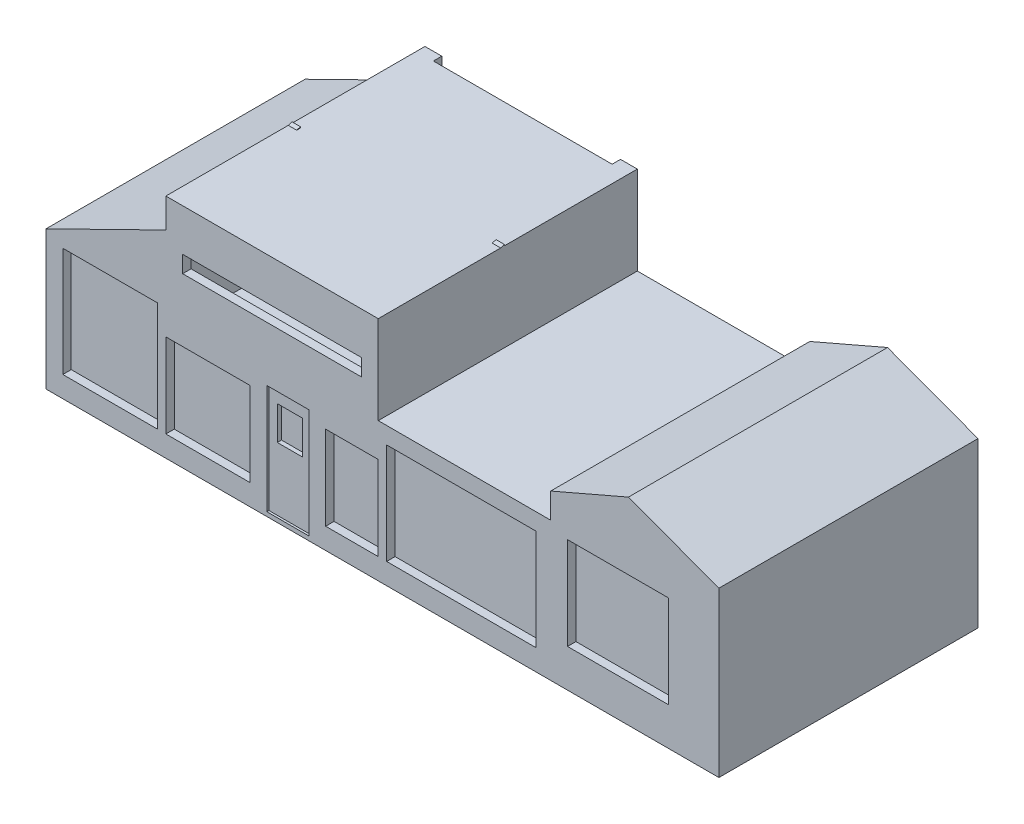
SolidWorks part; units mm, degrees
material "Plain Carbon Steel"
ref_plane "Front Plane" through (0, 0, 0) normal (0, 0, 1) x (1, 0, 0)
ref_plane "Top Plane" through (0, 0, 0) normal (0, 1, 0) x (1, 0, 0)
ref_plane "Right Plane" through (0, 0, 0) normal (1, 0, 0) x (0, 0, -1)
sketch "Sketch1" plane through (0, 0, 0) normal (0, 0, 1) x (1, 0, 0)
  line L1 (0, 0) -> (1016, 0)
  line L2 (0, 0) -> (0, 342.9)
  line L3 (0, 342.9) -> (1016, 342.9)
  line L4 (1016, 0) -> (1016, 342.9)
  dimension "D1" = 1016
  dimension "D2" = 342.9
extrude "Boss-Extrude1" add sketch "Sketch1" against normal blind 391.2
sketch "Right" plane through (0, 0, 0) normal (-1, 0, 0) x (0, 0, 1)
  line L8 (-25.4, 82.55) -> (-25.4, 184.15)
  line L9 (-25.4, 184.15) -> (-177.8, 184.15)
  line L10 (-177.8, 184.15) -> (-177.8, 82.55)
  line L11 (-177.8, 82.55) -> (-25.4, 82.55)
  line L16 (0, 0) -> (0, 209.55)
  line L17 (0, 209.55) -> (-203.2, 209.55)
  line L18 (-203.2, 209.55) -> (-203.2, 0)
  line L19 (-203.2, 0) -> (0, 0)
sketch "Front" plane through (0, 0, 0) normal (0, 0, 1) x (1, 0, 0)
  line L8 (0, 342.9) -> (0, 0)
  line L9 (0, 0) -> (1016, 0)
  line L10 (1016, 0) -> (1016, 342.9)
  line L11 (1016, 342.9) -> (0, 342.9)
  line L54 (1016, 0) -> (1016, 209.55)
  line L55 (0, 0) -> (1016, 0)
  line L56 (0, 209.55) -> (0, 0)
  line L57 (1016, 209.55) -> (501.65, 209.55)
  line L58 (501.65, 209.55) -> (501.65, 298.45)
  line L59 (501.65, 298.45) -> (180.975, 298.45)
  line L60 (0, 209.55) -> (180.975, 209.55)
  line L61 (180.975, 298.45) -> (180.975, 209.55)
  line L62 (180.975, 209.55) -> (0, 209.55)
  line L63 (180.975, 209.55) -> (180.975, 298.45)
  line L64 (180.975, 298.45) -> (0, 209.55)
  line L65 (25.4, 196.85) -> (168.275, 196.85)
  line L66 (168.275, 196.85) -> (25.4, 196.85)
  line L67 (168.275, 31.75) -> (168.275, 196.85)
  line L68 (25.4, 31.75) -> (168.275, 31.75)
  line L69 (25.4, 196.85) -> (25.4, 31.75)
  line L70 (25.4, 196.85) -> (25.4, 31.75)
  line L71 (762, 209.55) -> (1016, 209.55)
  line L72 (762, 247.65) -> (762, 209.55)
  line L73 (879.4142, 298.45) -> (762, 247.65)
  line L74 (1016, 247.65) -> (879.4142, 298.45)
  line L75 (1016, 209.55) -> (1016, 247.65)
  line L76 (501.65, 31.75) -> (501.65, 158.75)
  line L77 (501.65, 158.75) -> (422.275, 158.75)
  line L78 (422.275, 158.75) -> (422.275, 31.75)
  line L79 (422.275, 31.75) -> (501.65, 31.75)
  line L80 (333.375, 6.35) -> (396.875, 6.35)
  line L81 (396.875, 6.35) -> (396.875, 171.45)
  line L82 (396.875, 171.45) -> (333.375, 171.45)
  line L83 (333.375, 171.45) -> (333.375, 6.35)
  line L84 (180.975, 158.75) -> (180.975, 31.75)
  line L85 (307.975, 158.75) -> (180.975, 158.75)
  line L86 (307.975, 31.75) -> (307.975, 158.75)
  line L87 (180.975, 31.75) -> (307.975, 31.75)
  line L88 (476.25, 254) -> (476.25, 279.4)
  line L89 (476.25, 279.4) -> (206.375, 279.4)
  line L90 (206.375, 279.4) -> (206.375, 254)
  line L91 (206.375, 254) -> (476.25, 254)
  line L92 (787.4, 57.15) -> (939.8, 57.15)
  line L93 (787.4, 196.85) -> (787.4, 57.15)
  line L94 (939.8, 196.85) -> (787.4, 196.85)
  line L95 (939.8, 57.15) -> (939.8, 196.85)
  line L96 (514.35, 31.75) -> (739.775, 31.75)
  line L97 (514.35, 184.15) -> (514.35, 31.75)
  line L98 (739.775, 184.15) -> (514.35, 184.15)
  line L99 (739.775, 31.75) -> (739.775, 184.15)
sketch "Left" plane through (1016, 0, 0) normal (1, 0, 0) x (0, 0, -1)
  line L16 (190.5, 209.55) -> (190.5, 247.65)
  line L17 (190.5, 247.65) -> (12.7, 247.65)
  line L18 (203.2, 209.55) -> (203.2, 247.65)
  line L19 (203.2, 247.65) -> (190.5, 247.65)
  line L20 (190.5, 247.65) -> (190.5, 209.55)
  line L21 (12.7, 209.55) -> (190.5, 209.55)
  line L22 (190.5, 209.55) -> (203.2, 209.55)
  line L23 (12.7, 209.55) -> (12.7, 247.65)
  line L24 (0, 247.65) -> (0, 209.55)
  line L25 (12.7, 247.65) -> (0, 247.65)
  line L26 (12.7, 247.65) -> (12.7, 209.55)
  line L27 (0, 209.55) -> (12.7, 209.55)
  line L28 (203.2, 209.55) -> (0, 209.55)
  line L29 (203.2, 0) -> (203.2, 209.55)
  line L30 (0, 0) -> (203.2, 0)
  line L31 (0, 209.55) -> (0, 0)
sketch "Back" plane through (0, 0, -391.2) normal (0, 0, -1) x (-1, 0, 0)
  line L0 (-206.375, 342.9) -> (-476.25, 342.9)
  line L55 (-939.8, 196.85) -> (-939.8, 57.15)
  line L56 (-939.8, 57.15) -> (-787.4, 57.15)
  line L57 (-939.8, 196.85) -> (-939.8, 57.15)
  line L58 (-479.425, 158.75) -> (-479.425, 95.25)
  line L59 (-479.425, 95.25) -> (-314.325, 95.25)
  line L60 (-479.425, 95.25) -> (-314.325, 95.25)
  line L61 (-479.425, 158.75) -> (-479.425, 95.25)
  line L62 (-314.325, 158.75) -> (-479.425, 158.75)
  line L63 (-314.325, 95.25) -> (-314.325, 158.75)
  line L64 (-206.375, 241.3) -> (-206.375, 292.1)
  line L65 (-476.25, 241.3) -> (-206.375, 241.3)
  line L66 (-476.25, 241.3) -> (-206.375, 241.3)
  line L67 (-206.375, 292.1) -> (-476.25, 292.1)
  line L68 (-206.375, 292.1) -> (-476.25, 292.1)
  line L69 (-476.25, 292.1) -> (-476.25, 241.3)
  line L70 (-476.25, 292.1) -> (-476.25, 241.3)
  line L71 (-501.65, 298.45) -> (-501.65, 209.55)
  line L72 (-501.65, 209.55) -> (-1016, 209.55)
  line L73 (0, 0) -> (0, 209.55)
  line L74 (-1016, 0) -> (0, 0)
  line L75 (-1016, 209.55) -> (-1016, 0)
  line L76 (-180.975, 298.45) -> (-501.65, 298.45)
  line L77 (-488.95, 342.9) -> (-501.65, 342.9)
  line L78 (-501.65, 342.9) -> (-501.65, 298.45)
  line L79 (-501.65, 298.45) -> (-488.95, 298.45)
  line L80 (0, 209.55) -> (-180.975, 209.55)
  line L81 (-180.975, 209.55) -> (-180.975, 298.45)
  line L82 (-193.675, 298.45) -> (-180.975, 298.45)
  line L83 (-180.975, 298.45) -> (-180.975, 342.9)
  line L84 (0, 209.55) -> (-180.975, 298.45)
  line L85 (-180.975, 342.9) -> (-180.975, 298.45)
  line L86 (-180.975, 342.9) -> (-193.675, 342.9)
  line L87 (-488.95, 342.9) -> (-488.95, 298.45)
  line L88 (-488.95, 298.45) -> (-193.675, 298.45)
  line L89 (-488.95, 298.45) -> (-488.95, 342.9)
  line L90 (-193.675, 342.9) -> (-206.375, 342.9)
  line L91 (-206.375, 342.9) -> (-206.375, 304.8)
  line L92 (-206.375, 304.8) -> (-476.25, 304.8)
  line L93 (-476.25, 304.8) -> (-476.25, 342.9)
  line L94 (-476.25, 342.9) -> (-488.95, 342.9)
  line L95 (-193.675, 298.45) -> (-193.675, 342.9)
  line L96 (-193.675, 342.9) -> (-193.675, 298.45)
  line L97 (-787.4, 57.15) -> (-787.4, 196.85)
  line L98 (-787.4, 196.85) -> (-787.4, 57.15)
  line L99 (-787.4, 196.85) -> (-939.8, 196.85)
  line L100 (-787.4, 196.85) -> (-939.8, 196.85)
  line L101 (-1016, 209.55) -> (-762, 209.55)
  line L102 (-762, 209.55) -> (-762, 247.65)
  line L103 (-762, 247.65) -> (-879.4142, 298.45)
  line L104 (-879.4142, 298.45) -> (-1016, 247.65)
  line L105 (-1016, 247.65) -> (-1016, 209.55)
  line L106 (-590.55, 184.15) -> (-590.55, 158.75)
  line L107 (-590.55, 158.75) -> (-527.05, 158.75)
  line L108 (-527.05, 158.75) -> (-527.05, 184.15)
  line L109 (-527.05, 184.15) -> (-590.55, 184.15)
  line M1 (0, 0) -> (0, 342.9)
  line M2 (0, 342.9) -> (-1016, 342.9)
  line M3 (-1016, 342.9) -> (-1016, 0)
sketch "Sketch7" plane through (0, 0, -391.2) normal (0, 0, -1) x (-1, 0, 0)
  line L12 (-488.95, 361.95) -> (-488.95, 298.45)
  line L13 (-488.95, 298.45) -> (-193.675, 298.45)
  line L14 (-193.675, 298.45) -> (-193.675, 361.95)
  line L15 (-193.675, 361.95) -> (-488.95, 361.95)
  line L16 (-501.65, 361.95) -> (-501.65, 298.45)
  line L17 (-501.65, 298.45) -> (-488.95, 298.45)
  line L18 (-488.95, 298.45) -> (-488.95, 361.95)
  line L19 (-488.95, 361.95) -> (-501.65, 361.95)
  line L20 (-193.675, 361.95) -> (-193.675, 298.45)
  line L21 (-193.675, 298.45) -> (-180.975, 298.45)
  line L22 (-180.975, 298.45) -> (-180.975, 361.95)
  line L23 (-180.975, 361.95) -> (-193.675, 361.95)
  line L32 (-476.25, 292.1) -> (-476.25, 241.3)
  line L33 (-206.375, 292.1) -> (-476.25, 292.1)
  line L34 (-206.375, 241.3) -> (-206.375, 292.1)
  line L35 (-476.25, 241.3) -> (-206.375, 241.3)
  line L36 (-501.65, 298.45) -> (-501.65, 209.55)
  line L37 (-501.65, 209.55) -> (-1016, 209.55)
  line L38 (0, 209.55) -> (-180.975, 209.55)
  line L39 (-180.975, 209.55) -> (-180.975, 298.45)
extrude "Cut-Extrude1" cut sketch "Back" against normal through all contours L104 L103 L102 L72 L71 L78 M2 M3 | L84 L83 M1 M2 region at (75.4062, 294.7458, -391.2) region at (719.1949, 286.4423, -391.2)
sketch "Sketch11" plane through (29.8962, -69.0993, 0) normal (-0.3971, 0.9178, 0) x (0.9178, 0.3971, 0)
  line L12 (797.6879, 12.7) -> (925.6205, 12.7)
  line L13 (925.6205, 12.7) -> (925.6205, 190.5)
  line L14 (925.6205, 0) -> (925.6205, 12.7)
  line L15 (797.6879, 0) -> (925.6205, 0)
  line L16 (797.6879, 12.7) -> (797.6879, 0)
  line L17 (925.6205, 12.7) -> (797.6879, 12.7)
  line L18 (797.6879, 190.5) -> (797.6879, 12.7)
  line L19 (797.6879, 190.5) -> (925.6205, 190.5)
  line L20 (797.6879, 203.2) -> (797.6879, 190.5)
  line L21 (925.6205, 203.2) -> (797.6879, 203.2)
  line L22 (925.6205, 190.5) -> (925.6205, 203.2)
  line L23 (925.6205, 190.5) -> (797.6879, 190.5)
sketch "Sketch12" plane through (204.3794, 549.514, 0) normal (0.3486, 0.9373, 0) x (0.9373, -0.3486, 0)
  line L12 (865.9388, 190.5) -> (720.2119, 190.5)
  line L13 (720.2119, 190.5) -> (720.2119, 12.7)
  line L14 (720.2119, 203.2) -> (720.2119, 190.5)
  line L15 (865.9388, 203.2) -> (720.2119, 203.2)
  line L16 (865.9388, 190.5) -> (865.9388, 203.2)
  line L17 (720.2119, 190.5) -> (865.9388, 190.5)
  line L18 (865.9388, 12.7) -> (865.9388, 190.5)
  line L19 (720.2119, 12.7) -> (865.9388, 12.7)
  line L20 (865.9388, 0) -> (865.9388, 12.7)
  line L21 (720.2119, 0) -> (865.9388, 0)
  line L22 (720.2119, 12.7) -> (720.2119, 0)
  line L23 (865.9388, 12.7) -> (720.2119, 12.7)
extrude "Cut-Extrude4" cut sketch "Front" against normal blind 12.7 contours L90 L91 L88 L89 | L65 L69 L68 L67 | L84 L87 L86 L85 | L82 L83 L80 L81 | L78 L79 L76 L77 | L96 L99 L98 L97 | L92 L95 L94 L93 region at (96.8375, 114.3, 0) region at (461.9625, 95.25, 0) region at (365.125, 88.9, 0) region at (244.475, 95.25, 0) region at (341.3125, 266.7, 0) region at (863.6, 127, 0) region at (627.0625, 107.95, 0)
extrude "Cut-Extrude5" cut sketch "Right" against normal blind 12.7 contours L10 L11 L8 L9 region at (0, 133.35, -101.6)
extrude "Cut-Extrude6" cut sketch "Back<3>" against normal blind 12.7 contours L97 L99 L55 L56 | L108 L109 L106 L107 | L59 L63 L62 L58 | L93 L92 L91 M2 | L67 L69 L65 L64 region at (341.3125, 323.85, -391.2) region at (863.6, 127, -391.2) region at (396.875, 127, -391.2) region at (341.3125, 266.7, -391.2) region at (558.8, 171.45, -391.2)
sketch "Back<3>" plane through (0, 0, -391.2) normal (0, 0, -1) x (-1, 0, 0) same geometry as "Back"
sketch "Sketch18" plane through (0, 6.35, 0) normal (0, 1, 0) x (1, 0, 0)
  line L0 (193.675, 139.7) -> (244.475, 139.7)
  line L1 (1016, 190.5) -> (879.4142, 190.5) construction
  line L2 (333.375, 0) -> (396.875, 0)
  line L3 (396.875, 0) -> (396.875, 12.7)
  line L4 (396.875, 12.7) -> (965.2, 12.7)
  line L5 (396.875, 12.7) -> (396.875, 0) construction
  line L6 (333.375, 0) -> (396.875, 0) construction
  line L7 (0, 391.2) -> (1016, 391.2)
  line L8 (0, 391.2) -> (0, 0)
  line L9 (0, 0) -> (1016, 0)
  line L10 (1016, 391.2) -> (1016, 0)
  line L11 (12.7, 378.5) -> (1003.3, 378.5)
  line L12 (12.7, 378.5) -> (12.7, 12.7)
  line L13 (12.7, 12.7) -> (1003.3, 12.7)
  line L14 (1003.3, 378.5) -> (1003.3, 12.7)
  line L15 (492.125, 378.5) -> (492.125, 63.5)
  line L16 (692.15, 378.5) -> (692.15, 261.025)
  line L17 (501.65, 378.5) -> (501.65, 139.7)
  line L18 (518.8898, 139.7) -> (501.65, 139.7)
  line L19 (974.725, 378.5) -> (974.725, 12.7)
  line L20 (501.65, 130.175) -> (568.325, 130.175)
  line L21 (692.15, 261.025) -> (641.35, 261.025)
  line L22 (501.65, 130.175) -> (501.65, 73.025)
  line L23 (701.675, 292.775) -> (752.475, 292.775)
  line L24 (701.675, 292.775) -> (701.675, 261.025)
  line L25 (701.675, 261.025) -> (752.475, 261.025)
  line L26 (752.475, 292.775) -> (752.475, 261.025)
  line L27 (501.65, 73.025) -> (568.325, 73.025)
  line L28 (568.325, 130.175) -> (568.325, 73.025)
  line L29 (965.2, 38.1) -> (965.2, 165.1)
  line L30 (657.098, 311.825) -> (692.15, 311.825)
  line L31 (518.8898, 365.8) -> (518.8898, 152.4)
  line L32 (501.65, 63.5) -> (501.65, 12.7)
  line L33 (774.7, 378.5) -> (774.7, 12.7)
  line L34 (180.975, 378.5) -> (180.975, 12.7)
  line L35 (180.975, 0) -> (180.975, 391.2) construction
  line L36 (501.65, 0) -> (501.65, 391.2) construction
  line L37 (441.325, 114.3) -> (492.125, 114.3)
  line L38 (295.275, 139.7) -> (358.775, 139.7)
  line L39 (295.275, 139.7) -> (295.275, 378.5)
  line L40 (295.275, 378.5) -> (358.775, 378.5)
  line L41 (358.775, 139.7) -> (358.775, 378.5)
  line L42 (358.775, 378.5) -> (396.875, 378.5)
  line L43 (358.775, 378.5) -> (358.775, 139.7)
  line L44 (358.775, 139.7) -> (396.875, 139.7)
  line L45 (396.875, 378.5) -> (396.875, 139.7)
  line L46 (396.875, 378.5) -> (441.325, 378.5)
  line L47 (396.875, 378.5) -> (396.875, 139.7)
  line L48 (396.875, 139.7) -> (441.325, 139.7)
  line L49 (441.325, 378.5) -> (441.325, 139.7)
  line L50 (400.05, 177.8) -> (438.15, 177.8)
  line L51 (400.05, 177.8) -> (400.05, 152.4)
  line L52 (400.05, 152.4) -> (438.15, 152.4)
  line L53 (438.15, 177.8) -> (438.15, 152.4)
  line L54 (311.15, 365.8) -> (342.9, 365.8) construction
  line L55 (311.15, 365.8) -> (311.15, 340.4) construction
  line L56 (311.15, 340.4) -> (342.9, 340.4) construction
  line L57 (342.9, 365.8) -> (342.9, 340.4) construction
  line L58 (492.125, 63.5) -> (441.325, 63.5)
  line L59 (501.65, 63.5) -> (492.125, 63.5)
  line L60 (577.85, 63.5) -> (501.65, 63.5)
  line L61 (552.45, 130.175) -> (552.45, 79.375)
  line L62 (552.45, 79.375) -> (501.65, 79.375)
  line L89 (752.475, 184.15) -> (752.475, 378.5)
  line L90 (752.475, 378.5) -> (701.675, 378.5)
  line L91 (701.675, 378.5) -> (701.675, 302.3)
  line L92 (701.675, 302.3) -> (752.475, 302.3)
  line L93 (752.475, 302.3) -> (752.475, 308.65)
  line L94 (752.475, 308.65) -> (762, 308.65)
  line L95 (762, 308.65) -> (762, 251.5)
  line L96 (762, 251.5) -> (641.35, 251.5)
  line L97 (641.35, 251.5) -> (641.35, 311.825)
  line L98 (641.35, 311.825) -> (657.098, 311.825)
  line L99 (625.348, 343.575) -> (625.348, 378.5)
  line L100 (625.348, 378.5) -> (518.8898, 378.5)
  line L101 (518.8898, 378.5) -> (518.8898, 365.8)
  line L102 (518.8898, 152.4) -> (518.8898, 139.7)
  line L103 (518.8898, 139.7) -> (577.85, 139.7)
  line L104 (577.85, 139.7) -> (577.85, 63.5)
  line L106 (441.325, 63.5) -> (441.325, 139.7)
  line L107 (441.325, 139.7) -> (295.275, 139.7)
  line L108 (295.275, 139.7) -> (295.275, 88.9)
  line L109 (244.475, 88.9) -> (244.475, 190.5)
  line L110 (244.475, 190.5) -> (193.675, 190.5)
  line L111 (193.675, 190.5) -> (193.675, 139.7)
  line L112 (193.675, 139.7) -> (146.05, 139.7)
  line L113 (146.05, 139.7) -> (146.05, 165.1)
  line L114 (146.05, 165.1) -> (12.7, 165.1)
  line L115 (12.7, 165.1) -> (12.7, 152.4)
  line L116 (12.7, 152.4) -> (63.5, 152.4)
  line L117 (63.5, 152.4) -> (63.5, 63.5)
  line L118 (63.5, 63.5) -> (152.4, 63.5)
  line L119 (152.4, 63.5) -> (152.4, 12.7)
  line L120 (152.4, 12.7) -> (333.375, 12.7)
  line L121 (333.375, 12.7) -> (333.375, 0)
  line L125 (965.2, 12.7) -> (965.2, 38.1)
  line L126 (965.2, 38.1) -> (800.1, 38.1)
  line L127 (800.1, 38.1) -> (800.1, 165.1)
  line L128 (800.1, 165.1) -> (965.2, 165.1)
  line L129 (965.2, 165.1) -> (965.2, 190.5)
  line L130 (965.2, 190.5) -> (762, 190.5)
  line L131 (762, 190.5) -> (762, 184.15)
  line L132 (762, 184.15) -> (752.475, 184.15)
  circle A0 centre (311.15, 365.8) radius 9.525
  circle A1 centre (342.9, 365.8) radius 9.525
  circle A2 centre (311.15, 340.4) radius 9.525
  circle A3 centre (342.9, 340.4) radius 9.525
  arc A4 (625.348, 343.575) -> (657.098, 311.825) centre (657.098, 343.575) ccw
  arc A5 (244.475, 88.9) -> (295.275, 88.9) centre (269.875, 88.9) ccw
  ellipse E2 centre (524.1595, 259.1) end of major axis (524.1595, 150.8298) minor radius 31.0548 (518.8898, 152.4) -> (518.8898, 365.8) ccw
  dimension "D24" = 25.4
  dimension "D41" = 31.75
  dimension "D74" = 19.05
  dimension "D75" = 19.05
  dimension "D76" = 19.05
  dimension "D77" = 19.05
  dimension "D80" = 12.7
  dimension "D1" = 63.5
  dimension "D2" = 180.975
  dimension "D3" = 88.9
  dimension "D4" = 50.8
  dimension "D5" = 133.35
  dimension "D6" = 47.625
  dimension "D7" = 50.8
  dimension "D8" = 146.05
  dimension "D9" = 136.525
  dimension "D10" = 76.2
  dimension "D11" = 106.4582
  dimension "D12" = 165.1
  dimension "D13" = 9.525
  dimension "D14" = 120.65
  dimension "D15" = 15.748
  dimension "D16" = 50.8
  dimension "D17" = 9.525
  dimension "D18" = 9.525
  dimension "D19" = 50.8
  dimension "D20" = 203.2
  dimension "D21" = 25.4
  dimension "D22" = 76.2
  dimension "D23" = 12.7
  dimension "D25" = 12.7
  dimension "D26" = 25.4
  dimension "D27" = 50.8
  dimension "D28" = 50.8
  dimension "D29" = 101.6
  dimension "D30" = 76.2
  dimension "D31" = 34.925
  dimension "D32" = 60.325
  dimension "D33" = 57.15
  dimension "D34" = 6.35
  dimension "D35" = 76.2
  dimension "D36" = 25.4
  dimension "D37" = 568.325
  dimension "D38" = 12.7
  dimension "D39" = 50.8
  dimension "D40" = 88.9
  dimension "D42" = 12.7
  dimension "D43" = 12.7
  dimension "D44" = 12.7
  dimension "D45" = 12.7
  dimension "D46" = 6.35
  dimension "D47" = 9.525
  dimension "D48" = 9.525
  dimension "D49" = 25.4
  dimension "D50" = 238.8
  dimension "D51" = 38.1
  dimension "D52" = 25.4
  dimension "D53" = 9.525
  dimension "D54" = 9.525
  dimension "D55" = 50.8
  dimension "D56" = 9.525
  dimension "D57" = 9.525
  dimension "D58" = 9.525
  dimension "D59" = 9.525
  dimension "D60" = 50.8
  dimension "D61" = 9.525
  dimension "D62" = 9.525
  dimension "D63" = 9.525
  dimension "D64" = 63.5
  dimension "D66" = 35.052
  dimension "D67" = 38.1
  dimension "D68" = 44.45
  dimension "D69" = 38.1
  dimension "D70" = 25.4
  dimension "D71" = 3.175
  dimension "D72" = 12.7
  dimension "D73" = 238.8
  dimension "D78" = 31.75
  dimension "D79" = 25.4
  dimension "D81" = 15.875
  dimension "D82" = 50.8
  dimension "D83" = 50.8
  dimension "D84" = 50.8
  dimension "D86" = 50.8
sketch "Sketch19" plane through (0, 6.35, 0) normal (0, 1, 0) x (1, 0, 0)
  line L0 (295.275, 139.7) -> (250.825, 139.7)
  line L1 (307.975, 378.5) -> (307.975, 139.7)
  line L2 (12.7, 378.5) -> (1003.3, 378.5) construction
  line L3 (441.325, 139.7) -> (295.275, 139.7) construction
  line L18 (250.825, 190.5) -> (250.825, 139.7)
  line L19 (250.825, 139.7) -> (244.475, 139.7)
  line L20 (244.475, 139.7) -> (244.475, 88.9)
  line L21 (295.275, 88.9) -> (295.275, 139.7)
  line L22 (295.275, 139.7) -> (441.325, 139.7)
  line L23 (441.325, 139.7) -> (441.325, 127)
  line L24 (441.325, 127) -> (492.125, 127)
  line L25 (492.125, 127) -> (492.125, 190.5)
  line L26 (492.125, 190.5) -> (250.825, 190.5)
  line L172 (25.4, 12.7) -> (25.4, 15.24)
  line L173 (25.4, 15.24) -> (152.4, 15.24)
  line L174 (152.4, 15.24) -> (152.4, 63.5)
  line L175 (152.4, 63.5) -> (142.24, 63.5)
  line L176 (142.24, 63.5) -> (142.24, 22.86)
  line L177 (142.24, 22.86) -> (22.86, 22.86)
  line L178 (22.86, 22.86) -> (22.86, 142.24)
  line L179 (22.86, 142.24) -> (63.5, 142.24)
  line L180 (63.5, 142.24) -> (63.5, 152.4)
  line L181 (63.5, 152.4) -> (12.7, 152.4)
  line L182 (12.7, 152.4) -> (12.7, 25.4)
  line L183 (12.7, 25.4) -> (12.7, 12.7)
  line L184 (12.7, 12.7) -> (25.4, 12.7)
  line L185 (22.86, 22.86) -> (142.24, 22.86)
  line L186 (142.24, 22.86) -> (142.24, 63.5)
  line L187 (142.24, 63.5) -> (63.5, 63.5)
  line L188 (63.5, 63.5) -> (63.5, 142.24)
  line L189 (63.5, 142.24) -> (22.86, 142.24)
  line L190 (22.86, 142.24) -> (22.86, 22.86)
  line L191 (82.55, 114.3) -> (82.55, 82.55)
  line L192 (82.55, 82.55) -> (133.35, 82.55)
  line L193 (133.35, 82.55) -> (133.35, 114.3)
  line L194 (133.35, 114.3) -> (82.55, 114.3)
  line L195 (518.8898, 139.7) -> (518.8898, 153.0623)
  line L196 (518.8898, 177.1377) -> (518.8898, 190.5)
  line L197 (518.8898, 190.5) -> (501.65, 190.5)
  line L198 (501.65, 190.5) -> (501.65, 139.7)
  line L199 (501.65, 139.7) -> (518.8898, 139.7)
  line L200 (692.15, 190.5) -> (627.888, 190.5)
  line L201 (627.888, 190.5) -> (627.888, 155.575)
  line L202 (657.098, 126.365) -> (692.15, 126.365)
  line L203 (692.15, 126.365) -> (692.15, 190.5)
  line L204 (627.888, 155.575) -> (627.888, 190.5)
  line L205 (627.888, 190.5) -> (625.348, 190.5)
  line L206 (625.348, 190.5) -> (625.348, 155.575)
  line L207 (657.098, 123.825) -> (692.15, 123.825)
  line L208 (692.15, 123.825) -> (692.15, 126.365)
  line L209 (692.15, 126.365) -> (657.098, 126.365)
  line L210 (657.098, 123.825) -> (641.35, 123.825)
  line L211 (641.35, 123.825) -> (641.35, 73.025)
  line L212 (641.35, 73.025) -> (692.15, 73.025)
  line L213 (692.15, 73.025) -> (692.15, 123.825)
  line L214 (692.15, 123.825) -> (657.098, 123.825)
  line L215 (752.475, 73.025) -> (752.475, 104.775)
  line L216 (752.475, 104.775) -> (701.675, 104.775)
  line L217 (701.675, 104.775) -> (701.675, 73.025)
  line L218 (701.675, 73.025) -> (752.475, 73.025)
  line L219 (800.1, 165.1) -> (800.1, 38.1)
  line L220 (800.1, 38.1) -> (939.8, 38.1)
  line L221 (939.8, 38.1) -> (939.8, 165.1)
  line L222 (939.8, 165.1) -> (800.1, 165.1)
  line L223 (965.2, 38.1) -> (965.2, 165.1)
  line L224 (965.2, 165.1) -> (800.1, 165.1)
  line L225 (800.1, 165.1) -> (800.1, 38.1)
  line L226 (800.1, 38.1) -> (965.2, 38.1)
  line L227 (974.725, 12.7) -> (1003.3, 12.7)
  line L228 (1003.3, 12.7) -> (1003.3, 190.5)
  line L229 (1003.3, 190.5) -> (974.725, 190.5)
  line L230 (974.725, 190.5) -> (974.725, 12.7)
  line L231 (501.65, 130.175) -> (501.65, 73.025)
  line L232 (501.65, 73.025) -> (568.325, 73.025)
  line L233 (568.325, 73.025) -> (568.325, 130.175)
  line L234 (568.325, 130.175) -> (501.65, 130.175)
  arc A2 (244.475, 88.9) -> (295.275, 88.9) centre (269.875, 88.9) ccw
  arc A10 (627.888, 155.575) -> (657.098, 126.365) centre (657.098, 155.575) ccw
  arc A11 (625.348, 155.575) -> (657.098, 123.825) centre (657.098, 155.575) ccw
  arc A12 (627.888, 155.575) -> (657.098, 126.365) centre (657.098, 155.575) ccw
  ellipse E6 centre (539.75, 165.1) end of major axis (570.23, 165.1) minor radius 16.51 (518.8898, 153.0623) -> (518.8898, 177.1377) ccw
  dimension "D10" = 25.4
  dimension "D1" = 63.5
  dimension "D2" = 9.525
  dimension "D3" = 241.3
  dimension "D4" = 50.8
  dimension "D5" = 6.35
  dimension "D6" = 146.05
  dimension "D7" = 50.8
  dimension "D8" = 12.7
extrude "Cut-Extrude12" cut sketch "Sketch19" along normal blind 101.6 from offset 76.2 contours L198 L199 L197 | L223 L221 | L212 L213 L207 | L221 L222 L219 L220 | L201 A10 L202 L203 L200 | L233 L234 L231 L232 | L217 L218 L215 L216 | L194 L191 L192 L193 region at (530.2728, 6.35, -165.1) region at (661.2095, 6.35, -159.6201) region at (666.75, 6.35, -98.425) region at (727.075, 6.35, -88.9) region at (869.95, 6.35, -101.6) region at (952.5, 6.35, -101.6) region at (534.9875, 6.35, -101.6)
sketch "Sketch31" plane through (0, 171.45, 0) normal (0, -1, 0) x (1, 0, 0)
  line L30 (701.675, -73.025) -> (701.675, -104.775)
  line L31 (701.675, -104.775) -> (752.475, -104.775)
  line L32 (752.475, -104.775) -> (752.475, -73.025)
  line L33 (752.475, -73.025) -> (701.675, -73.025)
  line L34 (692.15, -73.025) -> (641.35, -73.025)
  line L35 (641.35, -73.025) -> (641.35, -123.825)
  line L36 (641.35, -123.825) -> (692.15, -123.825)
  line L37 (692.15, -123.825) -> (692.15, -73.025)
  line L38 (627.888, -155.575) -> (627.888, -190.5)
  line L39 (627.888, -190.5) -> (692.15, -190.5)
  line L40 (692.15, -190.5) -> (692.15, -126.365)
  line L41 (692.15, -126.365) -> (657.098, -126.365)
  line L42 (568.325, -130.175) -> (568.325, -73.025)
  line L43 (568.325, -73.025) -> (501.65, -73.025)
  line L44 (501.65, -73.025) -> (501.65, -130.175)
  line L45 (501.65, -130.175) -> (568.325, -130.175)
  line L46 (244.475, -190.5) -> (492.125, -190.5)
  line L47 (518.8898, -190.5) -> (501.65, -190.5)
  line L48 (692.15, -126.365) -> (692.15, -123.825)
  line L49 (627.888, -190.5) -> (625.348, -190.5)
  line L50 (939.8, -165.1) -> (939.8, -38.1)
  line L51 (965.2, -38.1) -> (965.2, -165.1)
  line L52 (577.85, -139.7) -> (577.85, -190.5)
  line L53 (295.275, -139.7) -> (244.475, -139.7)
  line L90 (396.875, 0) -> (333.375, 0)
  line L91 (396.875, -12.7) -> (396.875, 0)
  line L92 (965.2, -12.7) -> (396.875, -12.7)
  line L93 (965.2, -38.1) -> (965.2, -12.7)
  line L94 (800.1, -38.1) -> (965.2, -38.1)
  line L95 (800.1, -165.1) -> (800.1, -38.1)
  line L96 (965.2, -165.1) -> (800.1, -165.1)
  line L97 (965.2, -190.5) -> (965.2, -165.1)
  line L98 (762, -190.5) -> (965.2, -190.5)
  line L99 (762, -184.15) -> (762, -190.5)
  line L100 (752.475, -184.15) -> (762, -184.15)
  line L101 (752.475, -190.5) -> (752.475, -184.15)
  line L102 (701.675, -190.5) -> (752.475, -190.5)
  line L103 (701.675, -114.3) -> (701.675, -190.5)
  line L104 (752.475, -114.3) -> (701.675, -114.3)
  line L105 (752.475, -120.65) -> (752.475, -114.3)
  line L106 (762, -120.65) -> (752.475, -120.65)
  line L107 (762, -63.5) -> (762, -120.65)
  line L108 (641.35, -63.5) -> (762, -63.5)
  line L109 (641.35, -123.825) -> (641.35, -63.5)
  line L110 (657.098, -123.825) -> (641.35, -123.825)
  line L111 (625.348, -190.5) -> (625.348, -155.575)
  line L112 (518.8898, -190.5) -> (625.348, -190.5)
  line L113 (518.8898, -177.1377) -> (518.8898, -190.5)
  line L114 (518.8898, -139.7) -> (518.8898, -153.0623)
  line L115 (577.85, -139.7) -> (518.8898, -139.7)
  line L116 (577.85, -63.5) -> (577.85, -139.7)
  line L117 (441.325, -63.5) -> (577.85, -63.5)
  line L118 (441.325, -139.7) -> (441.325, -63.5)
  line L119 (295.275, -139.7) -> (441.325, -139.7)
  line L120 (295.275, -88.9) -> (295.275, -139.7)
  line L121 (244.475, -190.5) -> (244.475, -88.9)
  line L122 (193.675, -190.5) -> (244.475, -190.5)
  line L123 (193.675, -139.7) -> (193.675, -190.5)
  line L124 (146.05, -139.7) -> (193.675, -139.7)
  line L125 (146.05, -165.1) -> (146.05, -139.7)
  line L126 (12.7, -165.1) -> (146.05, -165.1)
  line L127 (12.7, -152.4) -> (12.7, -165.1)
  line L128 (63.5, -152.4) -> (12.7, -152.4)
  line L129 (63.5, -63.5) -> (63.5, -152.4)
  line L130 (152.4, -63.5) -> (63.5, -63.5)
  line L131 (152.4, -12.7) -> (152.4, -63.5)
  line L132 (333.375, -12.7) -> (152.4, -12.7)
  line L133 (333.375, 0) -> (333.375, -12.7)
  line L134 (1016, 0) -> (0, 0)
  line L135 (0, 0) -> (0, -203.2)
  line L136 (0, -203.2) -> (1016, -203.2)
  line L137 (1016, -203.2) -> (1016, 0)
  line L186 (180.9126, -12.7) -> (180.9126, -190.5)
  line L187 (180.9126, -190.5) -> (244.475, -190.5)
  line L188 (244.475, -190.5) -> (244.475, -88.9)
  line L189 (295.275, -88.9) -> (295.275, -139.7)
  line L190 (295.275, -139.7) -> (441.325, -139.7)
  line L191 (441.325, -139.7) -> (441.325, -127)
  line L192 (441.325, -127) -> (441.325, -63.5)
  line L193 (441.325, -63.5) -> (577.85, -63.5)
  line L194 (577.85, -63.5) -> (577.85, -139.7)
  line L195 (577.85, -139.7) -> (518.8898, -139.7)
  line L196 (518.8898, -139.7) -> (518.8898, -153.0623)
  line L197 (518.8898, -177.1377) -> (518.8898, -190.5)
  line L198 (518.8898, -190.5) -> (625.348, -190.5)
  line L199 (625.348, -190.5) -> (625.348, -155.575)
  line L200 (657.098, -123.825) -> (641.35, -123.825)
  line L201 (641.35, -123.825) -> (641.35, -73.025)
  line L202 (641.35, -73.025) -> (641.35, -63.5)
  line L203 (641.35, -63.5) -> (762, -63.5)
  line L204 (762, -63.5) -> (762, -120.65)
  line L205 (762, -120.65) -> (752.475, -120.65)
  line L206 (752.475, -120.65) -> (752.475, -114.3)
  line L207 (752.475, -114.3) -> (701.675, -114.3)
  line L208 (701.675, -114.3) -> (701.675, -190.5)
  line L209 (701.675, -190.5) -> (752.475, -190.5)
  line L210 (752.475, -190.5) -> (752.475, -184.15)
  line L211 (752.475, -184.15) -> (762, -184.15)
  line L212 (762, -184.15) -> (762, -190.5)
  line L213 (762, -190.5) -> (787.4, -190.5)
  line L214 (787.4, -190.5) -> (939.8, -190.5)
  line L215 (939.8, -190.5) -> (965.2, -190.5)
  line L216 (965.2, -190.5) -> (965.2, -165.1)
  line L217 (965.2, -165.1) -> (939.8, -165.1)
  line L218 (939.8, -165.1) -> (800.1, -165.1)
  line L219 (800.1, -165.1) -> (800.1, -38.1)
  line L220 (800.1, -38.1) -> (939.8, -38.1)
  line L221 (939.8, -38.1) -> (965.2, -38.1)
  line L222 (965.2, -38.1) -> (965.2, -12.7)
  line L223 (965.2, -12.7) -> (939.8, -12.7)
  line L224 (939.8, -12.7) -> (787.4, -12.7)
  line L225 (787.4, -12.7) -> (739.775, -12.7)
  line L226 (739.775, -12.7) -> (514.35, -12.7)
  line L227 (514.35, -12.7) -> (501.65, -12.7)
  line L228 (501.65, -12.7) -> (422.275, -12.7)
  line L229 (422.275, -12.7) -> (396.875, -12.7)
  line L230 (396.875, -12.7) -> (333.375, -12.7)
  line L231 (333.375, -12.7) -> (307.975, -12.7)
  line L232 (307.975, -12.7) -> (180.975, -12.7)
  line L233 (180.975, -12.7) -> (180.9126, -12.7)
  line L234 (701.675, -104.775) -> (701.675, -73.025)
  line L235 (692.15, -73.025) -> (692.15, -123.825)
  line L236 (692.15, -126.365) -> (692.15, -190.5)
  line L237 (568.325, -130.175) -> (501.65, -130.175)
  line L238 (492.125, -127) -> (492.125, -190.5)
  line L239 (501.65, -190.5) -> (501.65, -139.7)
  line L240 (501.65, -139.7) -> (518.8898, -139.7)
  line L241 (441.325, -127) -> (492.125, -127)
  line L242 (501.65, -190.5) -> (492.125, -190.5)
  line L244 (492.125, -127) -> (492.125, -63.5)
  arc A1 (657.098, -126.365) -> (627.888, -155.575) centre (657.098, -155.575) ccw
  arc A4 (657.098, -123.825) -> (625.348, -155.575) centre (657.098, -155.575) ccw
  arc A5 (295.275, -88.9) -> (244.475, -88.9) centre (269.875, -88.9) ccw
  arc A8 (295.275, -88.9) -> (244.475, -88.9) centre (269.875, -88.9) ccw
  arc A9 (657.098, -123.825) -> (625.348, -155.575) centre (657.098, -155.575) ccw
  ellipse E2 centre (539.75, -165.1) end of major axis (570.23, -165.1) minor radius 16.51 (518.8898, -177.1377) -> (518.8898, -153.0623) ccw
  ellipse E4 centre (539.75, -165.1) end of major axis (570.23, -165.1) minor radius 16.51 (518.8898, -177.1377) -> (518.8898, -153.0623) ccw
sketch "Sketch36" plane through (0, 0, -12.7) normal (0, 0, 1) x (1, 0, 0)
  line L8 (206.375, 279.4) -> (206.375, 254)
  line L9 (206.375, 254) -> (476.25, 254)
  line L10 (476.25, 254) -> (476.25, 279.4)
  line L11 (476.25, 279.4) -> (206.375, 279.4)
  line L18 (488.7994, 177.8) -> (193.675, 177.8)
  line L19 (193.675, 177.8) -> (193.675, 298.45)
  line L20 (193.675, 298.45) -> (488.95, 298.45)
  line L21 (488.95, 298.45) -> (488.95, 254)
  line L22 (488.95, 254) -> (476.25, 254)
  line L23 (476.25, 254) -> (476.25, 279.4)
  line L24 (476.25, 279.4) -> (206.375, 279.4)
  line L25 (206.375, 279.4) -> (206.375, 254)
  line L26 (206.375, 254) -> (488.7994, 254)
  line L27 (488.7994, 254) -> (488.7994, 177.8)
  line M5 (206.375, 279.4) -> (206.375, 254)
  line M6 (206.375, 254) -> (476.25, 254)
  line M7 (476.25, 254) -> (476.25, 279.4)
  line M8 (476.25, 279.4) -> (206.375, 279.4)
extrude "top room" cut sketch "Sketch36" against normal blind 177.8 contours L27 L22 L21 L20 L19 L18 M6 M5 M8 M7 | L9 M8 M5 M6 M7 region at (341.3125, 266.7, -12.7) region at (341.2536, 231.3228, -12.7)
sketch "Sketch39" plane through (180.975, 0, 0) normal (-1, 0, 0) x (0, 0, 1)
  line L7 (-190.5, 298.45) -> (-190.5, 344.6756)
  line L8 (-184.8182, 342.9) -> (-190.5, 342.9)
  line L9 (-190.5, 344.6756) -> (-83.2182, 311.15)
  line M2 (0, 342.9) -> (-391.2, 342.9)
  dimension "D1" = 46.2256
extrude "topsaide" add sketch "Sketch39" against normal blind 12.7 contours M2 region at (180.975, 343.4919, -188.6061)
sketch "Sketch40" plane through (501.65, 0, 0) normal (1, 0, 0) x (0, 0, -1)
  line L3 (190.5, 298.45) -> (190.5, 344.6756)
  line L4 (184.8182, 342.9) -> (190.5, 342.9)
  line L5 (190.5, 344.6756) -> (83.2182, 311.15)
  line M1 (391.2, 342.9) -> (0, 342.9)
extrude "topside" add sketch "Sketch40" against normal blind 12.7 contours M1 region at (501.65, 343.4919, -188.6061)
sketch "Sketch49" plane through (0, 171.45, 0) normal (0, 1, 0) x (1, 0, 0)
  line L0 (488.95, 139.7) -> (488.95, 190.5)
  line L5 (441.325, 139.7) -> (488.95, 139.7)
  line L8 (488.95, 139.7) -> (488.95, 190.5)
  line L10 (317.5, 190.5) -> (317.5, 139.7)
  line L11 (488.95, 190.5) -> (317.5, 190.5)
  line L18 (317.5, 139.7) -> (441.325, 139.7)
sketch "Sketch42" plane through (0, 6.35, 0) normal (0, 1, 0) x (1, 0, 0)
  line L4 (82.55, 114.3) -> (82.55, 82.55)
  line L5 (82.55, 82.55) -> (133.35, 82.55)
  line L6 (133.35, 82.55) -> (133.35, 114.3)
  line L7 (133.35, 114.3) -> (82.55, 114.3)
extrude "table" add sketch "Sketch42" along normal blind 50.8
extrude "Cut-Extrude35" cut sketch "Sketch31" along normal blind 88.9 contours L113 E2 L114 L240 L239 L47 | L44 L45 L42 L43 | L41 A1 L38 L39 L40 | L36 L37 L34 L35 | L32 L33 L30 L31 | L53 region at (727.075, 171.45, -88.9) region at (666.75, 171.45, -98.425) region at (661.2095, 171.45, -159.6201) region at (530.2728, 171.45, -165.1) region at (269.875, 171.45, -104.0983) region at (534.9875, 171.45, -101.6)
extrude "Cut-Extrude36" cut sketch "Sketch31<7>" along normal blind 114.3 contours E2 L113 L112 L52 L115 L114 | L113 E2 L114 L240 L239 L47 region at (548.3699, 171.45, -189.7217) region at (530.2728, 171.45, -165.1)
sketch "Sketch31<7>" plane through (0, 171.45, 0) normal (0, -1, 0) x (1, 0, 0) same geometry as "Sketch31"
sketch "Sketch76" plane through (0, 0, 0) normal (0, 0, 1) x (1, 0, 0)
  line L1 (333.375, 171.45) -> (396.875, 171.45)
  line L2 (333.375, 171.45) -> (333.375, 6.35)
  line L3 (333.375, 6.35) -> (396.875, 6.35)
  line L4 (396.875, 171.45) -> (396.875, 6.35)
  line L5 (346.075, 152.4) -> (384.175, 152.4)
  line L6 (346.075, 152.4) -> (346.075, 101.6)
  line L7 (346.075, 101.6) -> (384.175, 101.6)
  line L8 (384.175, 152.4) -> (384.175, 101.6)
  line L9 (16.44, 203.7687) -> (197.55, 203.7687)
  line L10 (16.44, 203.7687) -> (16.44, 23.7432)
  line L11 (16.44, 23.7432) -> (949.1024, 23.7432)
  line L12 (949.1024, 203.7687) -> (949.1024, 23.7432)
  line L13 (482.7712, 203.7687) -> (949.1024, 203.7687)
  line L14 (197.55, 288.359) -> (482.7712, 288.359)
  line L15 (197.55, 288.359) -> (197.55, 203.7687)
  line L17 (482.7712, 288.359) -> (482.7712, 203.7687)
  circle A0 centre (346.075, 82.55) radius 3.175
  line M20 (333.375, 6.35) -> (333.375, 171.45)
  line M21 (333.375, 171.45) -> (396.875, 171.45)
  line M22 (396.875, 171.45) -> (396.875, 6.35)
  line M23 (396.875, 6.35) -> (333.375, 6.35)
  dimension "D3" = 6.35
  dimension "D4" = 76.2
  dimension "D1" = 50.8
  dimension "D2" = 38.1
  dimension "D5" = 12.7
  dimension "D6" = 63.5
  dimension "D7" = 165.1
  dimension "D8" = 12.7
  dimension "D9" = 19.05
extrude "Boss-Extrude30" add sketch "Sketch76" against normal mid plane 6.35 from offset 6.35 separate body contours A0 L5 L8 L7 L6 M20 M23 M22 M21 | A0 | L11 L4 M20 M23 region at (365.2064, 89.9831, 0) region at (365.125, 15.0466, 0) region at (346.075, 82.55, 0) offset against normal yes
scale "Scale7" bodies to scale 191 143 scale about origin uniform scaling yes scale factor 0.25
scale "Scale8" bodies to scale 260 259 scale about origin uniform scaling yes scale factor 0.8
scale "Scale9" bodies to scale 261 262 scale about origin uniform scaling yes scale factor 1.1
